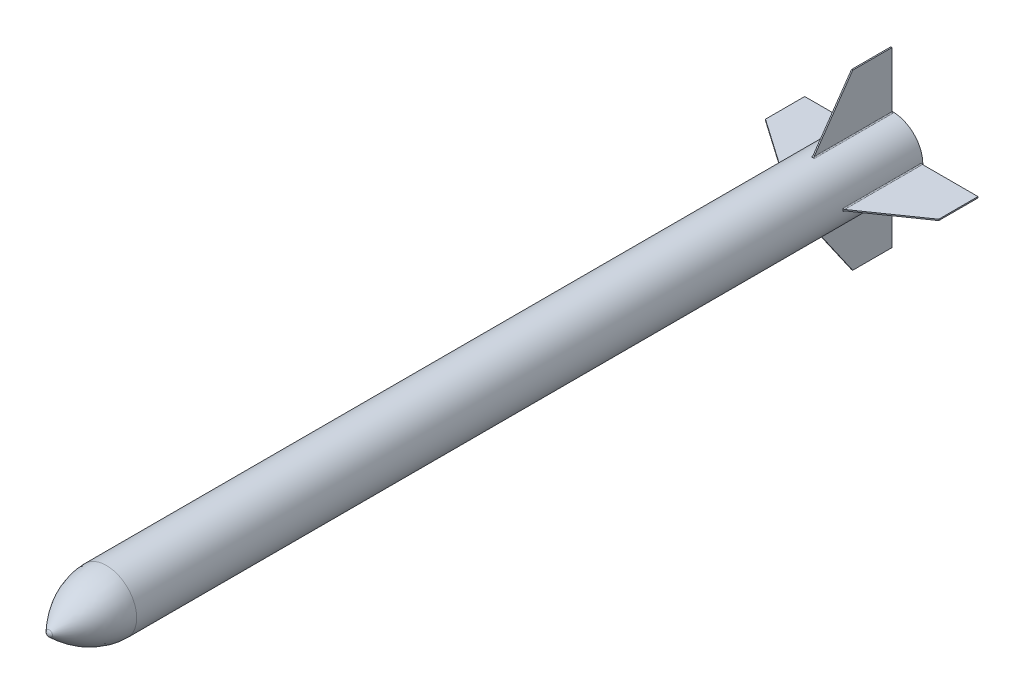
SolidWorks part; units mm, degrees
ref_plane "Front Plane" through (0, 0, 0) normal (0, 0, 1) x (1, 0, 0)
ref_plane "Top Plane" through (0, 0, 0) normal (0, 1, 0) x (1, 0, 0)
ref_plane "Right Plane" through (0, 0, 0) normal (1, 0, 0) x (0, 0, -1)
sketch "Sketch2" plane through (0, 0, 0) normal (1, 0, 0) x (0, 0, -1)
  line L0 (156.718, 78.3229) -> (2192.2105, 78.3229)
  line L1 (2192.2105, 78.3229) -> (2192.2105, 0)
  line L2 (2192.2105, 0) -> (4.9647, 0)
  line L3 (0, 0) -> (-156.718, 0) construction
  line L4 (0, 0) -> (2.1037, 78.3229) construction
  arc A0 (8.544, 8.3073) -> (4.9647, 0) centre (16.3947, 0) ccw
  spline S0 degree 2 poles (-3.4657, -3.5024) (84.0349, 85.892) (171.5354, 77.6228) knots 0 0 0 1 1 1 construction
  spline S1 degree 2 poles (8.544, 8.3073) (82.631, 78.3229) (156.718, 78.3229) knots 0.068626 0.068626 0.068626 0.91533 0.91533 0.91533
  point P11 (9.5915, 1.4354)
  point P12 (24.3632, 23.1081)
  point P14 (14.5979, 0)
  point P15 (4.9449, 0)
  point P16 (15.9371, 0)
  dimension "D4" = 11.43
  dimension "D1" = 2035.4925
  dimension "D2" = 156.718
  dimension "D3" = 78.3229
revolve "Revolve1" add sketch "Sketch2" angle 360 about L2
sketch "Sketch3" plane through (0, 0, -2192.2105) normal (0, 0, -1) x (-1, 0, 0)
  circle A0 centre (0, 0) radius 43.942
  dimension "D1" = 87.884
extrude "Boss-Extrude1" add sketch "Sketch3" along normal blind 15.24
ref_plane "Plane1" through (0, 254, 0) normal (0, 1, 0) x (1, 0, 0)
sketch "Sketch4" plane through (0, 254, 0) normal (0, 1, 0) x (1, 0, 0)
  line L1 (-1.5875, 1985.8355) -> (1.5875, 1985.8355)
  line L2 (-1.5875, 1985.8355) -> (-1.5875, 2189.0355)
  line L3 (-1.5875, 2189.0355) -> (1.5875, 2189.0355)
  line L4 (1.5875, 1985.8355) -> (1.5875, 2189.0355)
  line L5 (78.3229, 2192.2105) -> (-78.3229, 2192.2105) construction
  point P6 (0, 2189.0355)
  dimension "D1" = 3.175
  dimension "D2" = 3.175
  dimension "D3" = 203.2
extrude "Boss-Extrude2" add sketch "Sketch4" against normal up to surface (175.6932 mm away) up to face at (0, 78.3229, -156.718)
sketch "Sketch5" plane through (-1.5875, 0, 0) normal (-1, 0, 0) x (0, 0, 1)
  line L0 (-2189.0355, 224.3568) -> (-2087.4355, 224.3568)
  line L1 (-2189.0355, 78.3068) -> (-2189.0355, 254) construction
  line L2 (-2087.4355, 224.3568) -> (-1985.8355, 78.3068)
  line L3 (-1985.8355, 78.3068) -> (-1985.8355, 254)
  line L4 (-1985.8355, 254) -> (-2189.0355, 254)
  line L5 (-2189.0355, 254) -> (-2189.0355, 224.3568)
  dimension "D1" = 101.6
  dimension "D2" = 146.05
extrude "Cut-Extrude1" cut sketch "Sketch5" against normal up to next
fillet "Fillet1" radius 2.54 2 edges at (1.5875, 78.3068, -2087.4355) (-1.5875, 78.3068, -2087.4355)
pattern_circular "CirPattern1" count 4 over 360 about axis through (0, 0, -2192.2105) along (0, 0, -1) of "Cut-Extrude1", "Fillet1", "Boss-Extrude2"
equation "\"Body Tube Length\"= 80.1375"
equation "\"D1@Sketch2\"=\"Body Tube Length\""
equation "\"Retainer Diameter\"= 3.46"
equation "\"D1@Sketch3\"=\"Retainer Diameter\""
equation "\"Retainer Height\"= 0.6"
equation "\"D1@Boss-Extrude1\"=\"Retainer Height\""
equation "\"Fin Offset\"= .125"
equation "\"D1@Sketch4\"=\"Fin Offset\""
equation "\"Fin Thickness\"= .125"
equation "\"D2@Sketch4\"=\"Fin Thickness\""
equation "\"Fin Root Chord\"= 8"
equation "\"D3@Sketch4\"=\"Fin Root Chord\""
equation "\"Fin Tip Chord\"= 4"
equation "\"D1@Sketch5\"=\"Fin Tip Chord\""
equation "\"Fin Height\"= 5.75"
equation "\"D2@Sketch5\"=\"Fin Height\""
equation "\"Fin Epoxy Fillet Radius\"=0.1"
equation "\"D1@Fillet1\"=\"Fin Epoxy Fillet Radius\""
equation "\"Nosecone Length\" = 6.17"
equation "\"D2@Sketch2\"=\"Nosecone Length\""
equation "\"Rocket Radius\"=3.08358"
equation "\"D3@Sketch2\"= \"Rocket Radius\""
